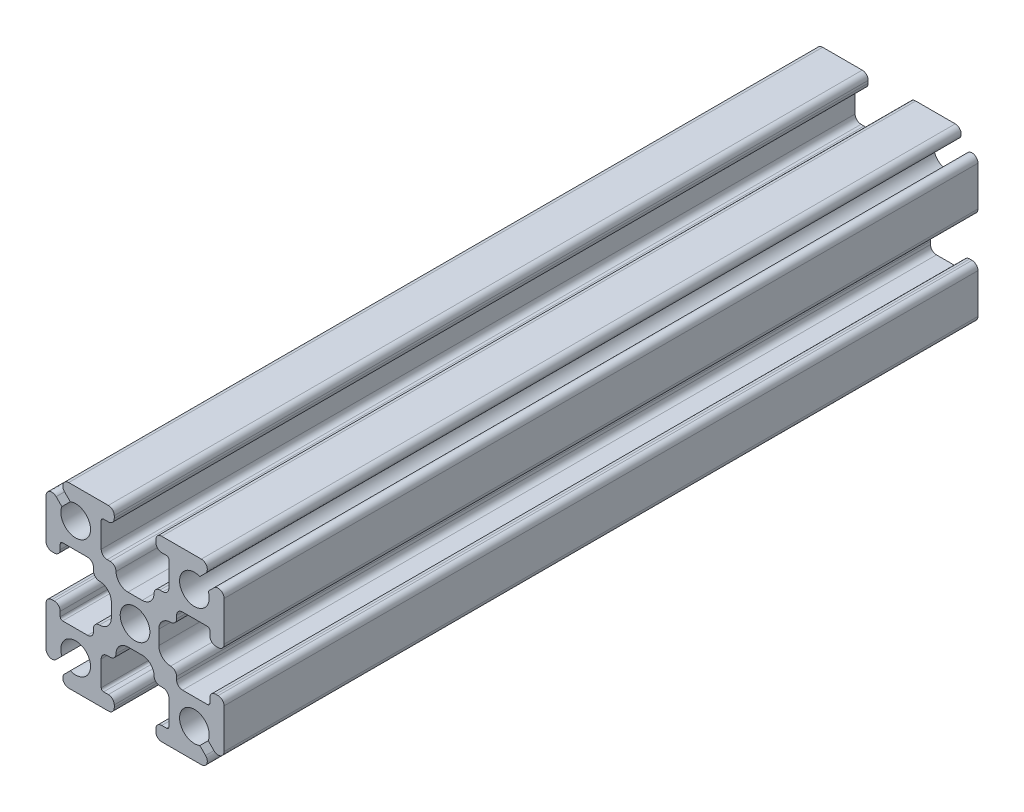
SolidWorks part; units mm, degrees
ref_plane "Front Plane" through (0, 0, 0) normal (0, 0, 1) x (1, 0, 0)
ref_plane "Top Plane" through (0, 0, 0) normal (0, 1, 0) x (1, 0, 0)
ref_plane "Right Plane" through (0, 0, 0) normal (1, 0, 0) x (0, 0, -1)
sketch "Sketch1" plane through (0, 0, 0) normal (0, 0, 1) x (1, 0, 0)
  line L0 (6.6464, 5.9393) -> (6.1636, 5.4565)
  line L1 (5.4565, 6.1636) -> (5.9393, 6.6464)
  line L2 (5.5858, 7.5) -> (2.25, 7.5)
  line L3 (1.75, 7) -> (1.75, 6.8)
  line L4 (2.25, 6.3) -> (2.65, 6.3)
  line L5 (2.85, 6.1) -> (2.85, 4)
  line L6 (2.35, 3.5) -> (2.1, 3.5)
  line L7 (0.6, 2) -> (-0.6, 2)
  line L8 (-2.1, 3.5) -> (-2.35, 3.5)
  line L9 (-2.85, 4) -> (-2.85, 6.1)
  line L10 (-2.65, 6.3) -> (-2.25, 6.3)
  line L11 (-1.75, 6.8) -> (-1.75, 7)
  line L12 (-2.25, 7.5) -> (-5.5858, 7.5)
  line L13 (-5.9393, 6.6464) -> (-5.4565, 6.1636)
  line L14 (-6.1636, 5.4565) -> (-6.6464, 5.9393)
  line L15 (-7.5, 5.5858) -> (-7.5, 2.25)
  line L16 (-7, 1.75) -> (-6.8, 1.75)
  line L17 (-6.3, 2.25) -> (-6.3, 2.65)
  line L18 (-6.1, 2.85) -> (-4, 2.85)
  line L19 (-3.5, 2.35) -> (-3.5, 2.1)
  line L20 (-2, 0.6) -> (-2, -0.6)
  line L21 (-3.5, -2.1) -> (-3.5, -2.35)
  line L22 (-4, -2.85) -> (-6.1, -2.85)
  line L23 (-6.3, -2.65) -> (-6.3, -2.25)
  line L24 (-6.8, -1.75) -> (-7, -1.75)
  line L25 (-7.5, -2.25) -> (-7.5, -5.5858)
  line L26 (-6.6464, -5.9393) -> (-6.1636, -5.4565)
  line L27 (-5.4565, -6.1636) -> (-5.9393, -6.6464)
  line L28 (-5.5858, -7.5) -> (-2.25, -7.5)
  line L29 (-1.75, -7) -> (-1.75, -6.8)
  line L30 (-2.25, -6.3) -> (-2.65, -6.3)
  line L31 (-2.85, -6.1) -> (-2.85, -4)
  line L32 (-2.35, -3.5) -> (-2.1, -3.5)
  line L33 (-0.6, -2) -> (0.6, -2)
  line L34 (2.1, -3.5) -> (2.35, -3.5)
  line L35 (2.85, -4) -> (2.85, -6.1)
  line L36 (2.65, -6.3) -> (2.25, -6.3)
  line L37 (1.75, -6.8) -> (1.75, -7)
  line L38 (2.25, -7.5) -> (5.5858, -7.5)
  line L39 (5.9393, -6.6464) -> (5.4565, -6.1636)
  line L40 (6.1636, -5.4565) -> (6.6464, -5.9393)
  line L41 (7.5, -5.5858) -> (7.5, -2.25)
  line L42 (7, -1.75) -> (6.8, -1.75)
  line L43 (6.3, -2.25) -> (6.3, -2.65)
  line L44 (6.1, -2.85) -> (4, -2.85)
  line L45 (3.5, -2.35) -> (3.5, -2.1)
  line L46 (2, -0.6) -> (2, 0.6)
  line L47 (3.5, 2.1) -> (3.5, 2.35)
  line L48 (4, 2.85) -> (6.1, 2.85)
  line L49 (6.3, 2.65) -> (6.3, 2.25)
  line L50 (6.8, 1.75) -> (7, 1.75)
  line L51 (7.5, 2.25) -> (7.5, 5.5858)
  circle A0 centre (0, 0) radius 1.25
  arc A1 (6.1636, 5.4565) -> (5.4565, 6.1636) centre (5, 5) cw
  arc A2 (5.9393, 6.6464) -> (5.5858, 7.5) centre (5.5858, 7) ccw
  arc A3 (2.25, 7.5) -> (1.75, 7) centre (2.25, 7) ccw
  arc A4 (1.75, 6.8) -> (2.25, 6.3) centre (2.25, 6.8) ccw
  arc A5 (2.65, 6.3) -> (2.85, 6.1) centre (2.65, 6.1) cw
  arc A6 (2.85, 4) -> (2.35, 3.5) centre (2.35, 4) cw
  arc A7 (2.1, 3.5) -> (1.6, 3) centre (2.1, 3) ccw
  arc A8 (1.6, 3) -> (0.6, 2) centre (0.6, 3) cw
  arc A9 (-0.6, 2) -> (-1.6, 3) centre (-0.6, 3) cw
  arc A10 (-1.6, 3) -> (-2.1, 3.5) centre (-2.1, 3) ccw
  arc A11 (-2.35, 3.5) -> (-2.85, 4) centre (-2.35, 4) cw
  arc A12 (-2.85, 6.1) -> (-2.65, 6.3) centre (-2.65, 6.1) cw
  arc A13 (-2.25, 6.3) -> (-1.75, 6.8) centre (-2.25, 6.8) ccw
  arc A14 (-1.75, 7) -> (-2.25, 7.5) centre (-2.25, 7) ccw
  arc A15 (-5.5858, 7.5) -> (-5.9393, 6.6464) centre (-5.5858, 7) ccw
  arc A16 (-5.4565, 6.1636) -> (-6.1636, 5.4565) centre (-5, 5) cw
  arc A17 (-6.6464, 5.9393) -> (-7.5, 5.5858) centre (-7, 5.5858) ccw
  arc A18 (-7.5, 2.25) -> (-7, 1.75) centre (-7, 2.25) ccw
  arc A19 (-6.8, 1.75) -> (-6.3, 2.25) centre (-6.8, 2.25) ccw
  arc A20 (-6.3, 2.65) -> (-6.1, 2.85) centre (-6.1, 2.65) cw
  arc A21 (-4, 2.85) -> (-3.5, 2.35) centre (-4, 2.35) cw
  arc A22 (-3.5, 2.1) -> (-3, 1.6) centre (-3, 2.1) ccw
  arc A23 (-3, 1.6) -> (-2, 0.6) centre (-3, 0.6) cw
  arc A24 (-2, -0.6) -> (-3, -1.6) centre (-3, -0.6) cw
  arc A25 (-3, -1.6) -> (-3.5, -2.1) centre (-3, -2.1) ccw
  arc A26 (-3.5, -2.35) -> (-4, -2.85) centre (-4, -2.35) cw
  arc A27 (-6.1, -2.85) -> (-6.3, -2.65) centre (-6.1, -2.65) cw
  arc A28 (-6.3, -2.25) -> (-6.8, -1.75) centre (-6.8, -2.25) ccw
  arc A29 (-7, -1.75) -> (-7.5, -2.25) centre (-7, -2.25) ccw
  arc A30 (-7.5, -5.5858) -> (-6.6464, -5.9393) centre (-7, -5.5858) ccw
  arc A31 (-6.1636, -5.4565) -> (-5.4565, -6.1636) centre (-5, -5) cw
  arc A32 (-5.9393, -6.6464) -> (-5.5858, -7.5) centre (-5.5858, -7) ccw
  arc A33 (-2.25, -7.5) -> (-1.75, -7) centre (-2.25, -7) ccw
  arc A34 (-1.75, -6.8) -> (-2.25, -6.3) centre (-2.25, -6.8) ccw
  arc A35 (-2.65, -6.3) -> (-2.85, -6.1) centre (-2.65, -6.1) cw
  arc A36 (-2.85, -4) -> (-2.35, -3.5) centre (-2.35, -4) cw
  arc A37 (-2.1, -3.5) -> (-1.6, -3) centre (-2.1, -3) ccw
  arc A38 (-1.6, -3) -> (-0.6, -2) centre (-0.6, -3) cw
  arc A39 (0.6, -2) -> (1.6, -3) centre (0.6, -3) cw
  arc A40 (1.6, -3) -> (2.1, -3.5) centre (2.1, -3) ccw
  arc A41 (2.35, -3.5) -> (2.85, -4) centre (2.35, -4) cw
  arc A42 (2.85, -6.1) -> (2.65, -6.3) centre (2.65, -6.1) cw
  arc A43 (2.25, -6.3) -> (1.75, -6.8) centre (2.25, -6.8) ccw
  arc A44 (1.75, -7) -> (2.25, -7.5) centre (2.25, -7) ccw
  arc A45 (5.5858, -7.5) -> (5.9393, -6.6464) centre (5.5858, -7) ccw
  arc A46 (5.4565, -6.1636) -> (6.1636, -5.4565) centre (5, -5) cw
  arc A47 (6.6464, -5.9393) -> (7.5, -5.5858) centre (7, -5.5858) ccw
  arc A48 (7.5, -2.25) -> (7, -1.75) centre (7, -2.25) ccw
  arc A49 (6.8, -1.75) -> (6.3, -2.25) centre (6.8, -2.25) ccw
  arc A50 (6.3, -2.65) -> (6.1, -2.85) centre (6.1, -2.65) cw
  arc A51 (4, -2.85) -> (3.5, -2.35) centre (4, -2.35) cw
  arc A52 (3.5, -2.1) -> (3, -1.6) centre (3, -2.1) ccw
  arc A53 (3, -1.6) -> (2, -0.6) centre (3, -0.6) cw
  arc A54 (2, 0.6) -> (3, 1.6) centre (3, 0.6) cw
  arc A55 (3, 1.6) -> (3.5, 2.1) centre (3, 2.1) ccw
  arc A56 (3.5, 2.35) -> (4, 2.85) centre (4, 2.35) cw
  arc A57 (6.1, 2.85) -> (6.3, 2.65) centre (6.1, 2.65) cw
  arc A58 (6.3, 2.25) -> (6.8, 1.75) centre (6.8, 2.25) ccw
  arc A59 (7, 1.75) -> (7.5, 2.25) centre (7, 2.25) ccw
  arc A60 (7.5, 5.5858) -> (6.6464, 5.9393) centre (7, 5.5858) ccw
extrude "Boss-Extrude1" add sketch "Sketch1" along normal blind 63.5
